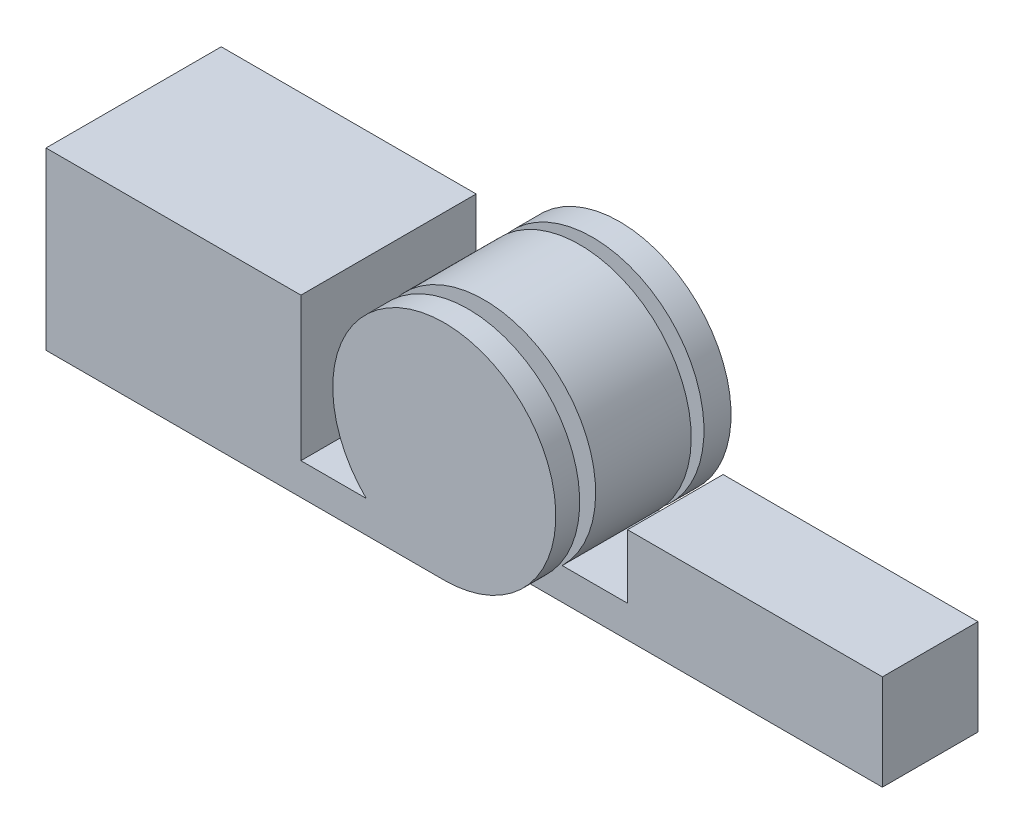
SolidWorks part; units mm, degrees
ref_plane "Front Plane" through (0, 0, 0) normal (0, 0, 1) x (1, 0, 0)
ref_plane "Top Plane" through (0, 0, 0) normal (0, 1, 0) x (1, 0, 0)
ref_plane "Right Plane" through (0, 0, 0) normal (1, 0, 0) x (0, 0, -1)
sketch "Sketch1" plane through (0, 0, 0) normal (0, 0, 1) x (1, 0, 0)
  line L1 (0, 0) -> (203.2, 0)
  line L2 (0, 0) -> (0, 139.7)
  line L3 (0, 139.7) -> (203.2, 139.7)
  line L4 (203.2, 25.4) -> (203.2, 139.7)
  line L5 (203.2, 0) -> (317.5, 0)
  line L7 (203.2, 25.4) -> (255.283, 25.4)
  arc A0 (317.5, 0) -> (255.283, 25.4) centre (317.5, 88.9) ccw
  dimension "D5" = 88.9
  dimension "D1" = 203.2
  dimension "D2" = 139.7
  dimension "D3" = 114.3
  dimension "D4" = 25.4
extrude "Boss-Extrude1" add sketch "Sketch1" along normal blind 139.7
ref_plane "Plane1" through (0, 0, 69.85) normal (0, 0, 1) x (1, 0, 0)
sketch "Sketch2" plane through (0, 0, 69.85) normal (0, 0, 1) x (1, 0, 0)
  circle A0 centre (317.5, 88.9) radius 88.9
  arc A1 (317.5, 0) -> (255.283, 25.4) centre (317.5, 88.9) ccw construction
  dimension "D1" = 177.8
extrude "Cut-Extrude1" cut sketch "Sketch2" against normal offset from surface 21.59 and the other way offset from surface 19.05 up to face at (173.9821, 81.4509, 0) other way up to face at (173.9821, 81.4509, 139.7)
sketch "Sketch3" plane through (0, 0, 0) normal (0, 0, 1) x (1, 0, 0)
  line L2 (406.4, 88.9) -> (406.4, 203.2)
  line L4 (381, 151.117) -> (381, 203.2)
  line L5 (381, 203.2) -> (330.2, 203.2)
  line L6 (406.4, 203.2) -> (406.4, 406.4)
  line L7 (406.4, 406.4) -> (330.2, 406.4)
  line L8 (330.2, 203.2) -> (330.2, 406.4)
  arc A0 (381, 151.117) -> (406.4, 88.9) centre (317.5, 88.9) ccw
  arc A3 (317.5, 0) -> (255.283, 25.4) centre (317.5, 88.9) ccw construction
  dimension "D5" = 88.9
  dimension "D1" = 203.2
  dimension "D2" = 114.3
  dimension "D3" = 25.4
  dimension "D4" = 76.2
extrude "Boss-Extrude2" [suppressed] add sketch "Sketch3" along normal blind 76.2 from offset 31.75 contours L6 L7 L8 L5 L4 A0 L2
sketch "Sketch5" plane through (0, 0, 69.85) normal (0, 0, 1) x (1, 0, 0)
  line L1 (317.5, 0) -> (431.8, 0)
  line L3 (379.717, 25.4) -> (431.8, 25.4)
  line L5 (431.8, 0) -> (635, 0)
  line L6 (431.8, 25.4) -> (431.8, 76.2)
  line L7 (431.8, 76.2) -> (635, 76.2)
  line L8 (635, 0) -> (635, 76.2)
  arc A0 (379.717, 25.4) -> (317.5, 0) centre (317.5, 88.9) ccw
  arc A1 (317.5, 0) -> (255.283, 25.4) centre (317.5, 88.9) ccw construction
  dimension "D1" = 88.9
  dimension "D2" = 114.3
  dimension "D3" = 203.2
  dimension "D4" = 76.2
  dimension "D5" = 25.4
extrude "Boss-Extrude3" add sketch "Sketch5" against normal blind 38.1 and the other way blind 38.1
